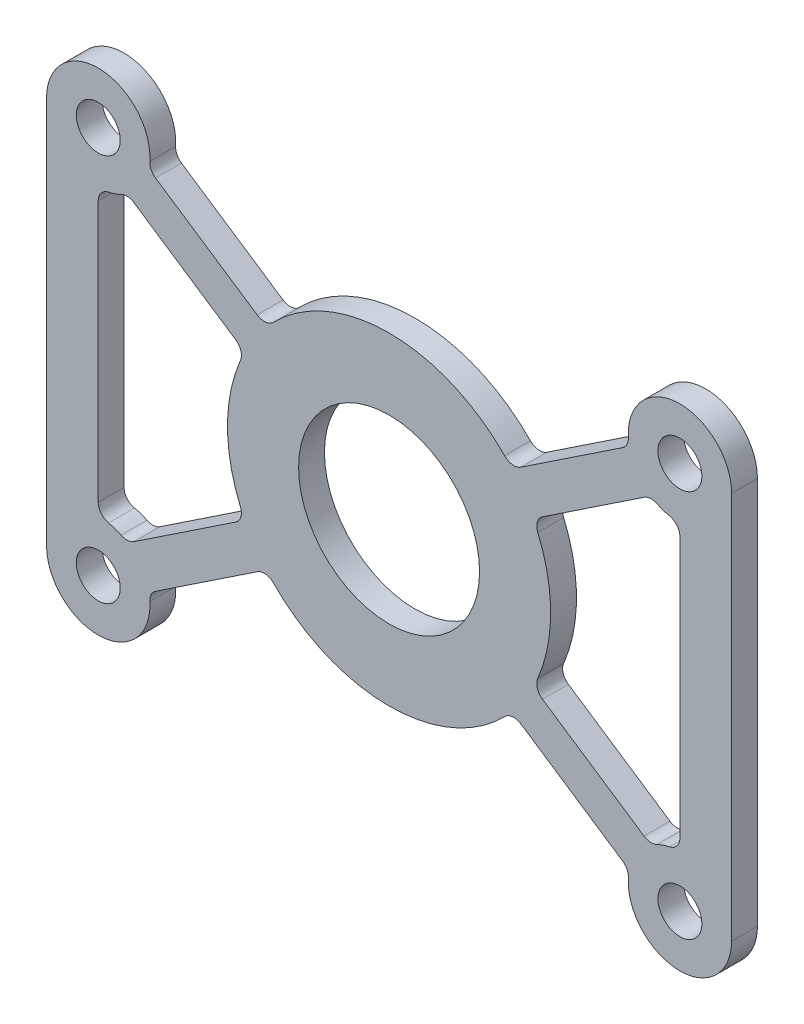
SolidWorks part; units mm, degrees
material "A2017"
ref_plane "正面" through (0, 0, 0) normal (0, 0, 1) x (1, 0, 0)
ref_plane "平面" through (0, 0, 0) normal (0, 1, 0) x (1, 0, 0)
ref_plane "右側面" through (0, 0, 0) normal (1, 0, 0) x (0, 0, -1)
sketch "ｽｹｯﾁ1" plane through (0, 0, 0) normal (0, 0, 1) x (1, 0, 0)
  circle A0 centre (0, 0) radius 12.5
  circle A1 centre (-22.5, 15) radius 4
  circle A2 centre (-22.5, -15) radius 4
  circle A3 centre (22.5, -15) radius 4
  circle A4 centre (22.5, 15) radius 4
  arc A5 (-26.1198, -13.2978) -> (-26.5, -15.0192) centre (-22.5, -15) ccw construction
  point P19 (-22.5, -15)
  dimension "D1" = 25
extrude "ﾎﾞｽ - 押し出し1" add sketch "ｽｹｯﾁ1" along normal blind 2
sketch "ｽｹｯﾁ2" plane through (0, 0, 2) normal (0, 0, 1) x (1, 0, 0)
  line L1 (-22.5, -15) -> (-26.5, -15)
  line L2 (-22.5, -15) -> (-22.5, 15)
  line L3 (-22.5, 15) -> (-26.5, 15)
  line L4 (-26.5, -15) -> (-26.5, 15)
  line L5 (26.5, -15) -> (22.5, -15)
  line L6 (26.5, -15) -> (26.5, 15)
  line L7 (26.5, 15) -> (22.5, 15)
  line L8 (22.5, -15) -> (22.5, 15)
  circle A0 centre (-22.5, 15) radius 4 construction
  circle A1 centre (22.5, -15) radius 4 construction
  circle A3 centre (22.5, 15) radius 4 construction
  circle A4 centre (-22.5, -15) radius 4 construction
  circle A5 centre (22.5, -15) radius 4
  circle A6 centre (22.5, 15) radius 4
  circle A7 centre (-22.5, 15) radius 4
  circle A8 centre (-22.5, -15) radius 4
extrude "ﾎﾞｽ - 押し出し2" add sketch "ｽｹｯﾁ2" against normal up to surface (2 mm away) contours A8 L2 A7 L4 | A8 A5 | A6 L8 A5 L6 region at (-24.5801, 0, 2) region at (24.5801, 0, 2) up to face at (12.5, 0, 0)
sketch "ｽｹｯﾁ3" plane through (0, 0, 2) normal (0, 0, 1) x (1, 0, 0)
  line L0 (-22.5, 15) -> (22.5, -15) construction
  line L1 (-21.6679, 16.2481) -> (23.3321, -13.7519)
  line L2 (-23.3321, 13.7519) -> (21.6679, -16.2481)
  line L3 (-22.5, -15) -> (22.5, 15) construction
  line L4 (-23.3321, -13.7519) -> (21.6679, 16.2481)
  line L5 (-21.6679, -16.2481) -> (23.3321, 13.7519)
  line L6 (-18.0547, -13.8392) -> (-8.081, -7.1901) construction
  arc A0 (-21.6679, 16.2481) -> (-23.3321, 13.7519) centre (-22.5, 15) ccw
  arc A1 (21.6679, -16.2481) -> (23.3321, -13.7519) centre (22.5, -15) ccw
  arc A2 (-23.3321, -13.7519) -> (-21.6679, -16.2481) centre (-22.5, -15) ccw
  arc A3 (23.3321, 13.7519) -> (21.6679, 16.2481) centre (22.5, 15) ccw
  circle A5 centre (0, 0) radius 12.5
  circle A6 centre (0, 0) radius 12.5
  point P4 (0, 0)
  point P9 (0, 0)
  circle M3 centre (0, 0) radius 12.5
  dimension "D1" = 0
extrude "ﾎﾞｽ - 押し出し3" add sketch "ｽｹｯﾁ3" against normal through all contours L4 A2 L5 M3 | L2 A1 L1 M3 | L1 A0 L2 M3 | L5 A3 L4 M3 region at (-16.9309, 11.2872, 2) region at (16.9309, 11.2872, 2) region at (-16.9309, -11.2872, 2) region at (16.9309, -11.2872, 2)
fillet "ﾌｨﾚｯﾄ1" radius 1 20 edges at (-18.5826, -14.1912, 1) (-9.4934, -8.1317, 1) (9.4934, -8.1317, 1) (18.5826, -14.1912, 1) (-11.1575, -5.6356, 1) (-20.2467, -11.695, 1) (-22.5, -11, 1) (-22.5, 11, 1) (-20.2467, 11.695, 1) (-11.1575, 5.6356, 1) (22.5, 11, 1) (22.5, -11, 1) (20.2467, -11.695, 1) (11.1575, -5.6356, 1) (11.1575, 5.6356, 1) (20.2467, 11.695, 1) (-9.4934, 8.1317, 1) (18.5826, 14.1912, 1) (9.4934, 8.1317, 1) (-18.5826, 14.1912, 1)
sketch "ｽｹｯﾁ5" plane through (0, 0, 0) normal (0, 0, -1) x (-1, 0, 0)
  circle A1 centre (0, 0) radius 7
  dimension "D1" = 14
extrude "ｶｯﾄ - 押し出し1" cut sketch "ｽｹｯﾁ5" against normal through all
hole_wizard "M3 すきま穴1" positions "ｽｹｯﾁ10" profile "ｽｹｯﾁ11" hole size "M3" standard "JIS" end condition through all
sketch "ｽｹｯﾁ10" plane through (0, 0, 2) normal (0, 0, 1) x (1, 0, 0)
  point P0 (-22.5, 15)
  point P3 (-22.5, -15)
  point P6 (22.5, -15)
  point P9 (22.5, 15)
sketch "ｽｹｯﾁ11" plane through (-22.5, 15, 2) normal (1, 0, 0) x (0, -1, 0)
  line L0 (0, 0) -> (0, 2)
  line L1 (0, 2) -> (1.7, 2)
  line L2 (1.7, 2) -> (1.7, 0)
  line L5 (1.7, 0) -> (0, 0)
  line L11 (0, -6.35) -> (0, 107.95) construction
  dimension "通し穴の直径" = 3.4
  dimension "通し穴の深さ" = 2
